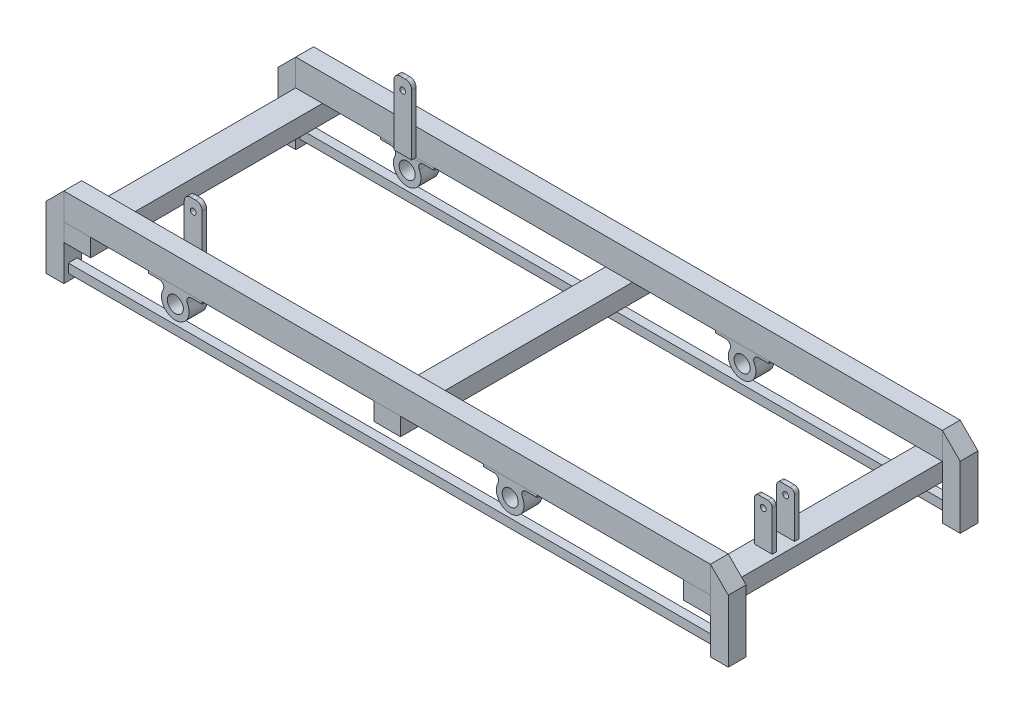
SolidWorks part; units mm, degrees
ref_plane "Front Plane" through (0, 0, 0) normal (0, 0, 1) x (1, 0, 0)
ref_plane "Top Plane" through (0, 0, 0) normal (0, 1, 0) x (1, 0, 0)
ref_plane "Right Plane" through (0, 0, 0) normal (1, 0, 0) x (0, 0, -1)
sketch "Sketch1" plane through (0, 0, 0) normal (0, 1, 0) x (1, 0, 0)
  line L0 (0, 236.3265) -> (0, -239.5918) construction
  line L1 (-360.8163, 0) -> (346.9388, 0) construction
  line L2 (-765, 280) -> (-725, 280)
  line L3 (-765, 280) -> (-765, 240)
  line L4 (-765, 240) -> (-725, 240)
  line L5 (-725, 280) -> (-725, 240)
  line L6 (-725, -280) -> (-725, -240)
  line L7 (-765, -240) -> (-725, -240)
  line L8 (-765, -280) -> (-765, -240)
  line L9 (-765, -280) -> (-725, -280)
  line L10 (765, -280) -> (725, -280)
  line L11 (765, -280) -> (765, -240)
  line L12 (765, -240) -> (725, -240)
  line L13 (725, -280) -> (725, -240)
  line L14 (725, 280) -> (725, 240)
  line L15 (765, 240) -> (725, 240)
  line L16 (765, 280) -> (765, 240)
  line L17 (765, 280) -> (725, 280)
  point P9 (-765, 260)
  dimension "D1" = 40
  dimension "D2" = 560
  dimension "D3" = 1530
extrude "Boss-Extrude1" add sketch "Sketch1" against normal blind 180
chamfer "Chamfer1" distance 40 angle 45 1 edges at (-765, 0, -260)
chamfer "Chamfer2" distance 40 angle 45 1 edges at (-765, 0, 260)
chamfer "Chamfer3" distance 40 angle 45 1 edges at (765, 0, -260)
chamfer "Chamfer4" distance 40 angle 45 1 edges at (765, 0, 260)
sketch "Sketch2" plane through (0, 0, 280) normal (0, 0, 1) x (1, 0, 0)
  line L0 (725, -180) -> (725, 0) construction
  line L1 (-725, 0) -> (725, 0)
  line L2 (-725, 0) -> (-725, -60)
  line L3 (-725, -60) -> (725, -60)
  line L4 (725, 0) -> (725, -60)
  dimension "D1" = 60
extrude "Boss-Extrude2" add sketch "Sketch2" against normal blind 40 separate body
mirror "Mirror2" about plane through (0, 0, 0) normal (0, 0, 1) of bodies 105
sketch "Sketch3" plane through (0, 0, 280) normal (0, 0, 1) x (1, 0, 0)
  line L0 (0, 430.6233) -> (0, -418.6092) construction
  line L1 (725, -60) -> (665, -60)
  line L2 (725, -60) -> (725, -100)
  line L3 (725, -100) -> (665, -100)
  line L4 (665, -60) -> (665, -100)
  line L5 (-665, -60) -> (-665, -100)
  line L6 (-725, -100) -> (-665, -100)
  line L7 (-725, -60) -> (-725, -100)
  line L8 (-725, -60) -> (-665, -60)
  line L9 (-725, -60) -> (725, -60) construction
  line L10 (-30, -60) -> (30, -60)
  line L11 (-30, -60) -> (-30, -100)
  line L12 (-30, -100) -> (30, -100)
  line L13 (30, -60) -> (30, -100)
  dimension "D1" = 60
  dimension "D2" = 40
  dimension "D3" = 40
  dimension "D4" = 60
extrude "Boss-Extrude3" add sketch "Sketch3" against normal up to surface (560 mm away) separate body up to face at (0, -30, -280)
sketch "Sketch4" plane through (-725, 0, 0) normal (1, 0, 0) x (0, 0, -1)
  line L0 (-260, 0) -> (-260, -180) construction
  line L1 (-270, -145) -> (-250, -145)
  line L2 (-270, -145) -> (-270, -165)
  line L3 (-270, -165) -> (-250, -165)
  line L4 (-250, -145) -> (-250, -165)
  line L5 (-270, -145) -> (-250, -165) construction
  line L6 (-270, -165) -> (-250, -145) construction
  line L7 (-240, 0) -> (-280, 0) construction
  line L8 (-280, -180) -> (-240, -180) construction
  line L9 (0, 126.0485) -> (0, -222.351) construction
  line L10 (270, -165) -> (250, -145) construction
  line L11 (270, -145) -> (250, -165) construction
  line L12 (250, -145) -> (250, -165)
  line L13 (270, -165) -> (250, -165)
  line L14 (270, -145) -> (270, -165)
  line L15 (270, -145) -> (250, -145)
  point P0 (-260, -155)
  point P18 (260, -155)
  dimension "D1" = 20
  dimension "D2" = 25
extrude "Boss-Extrude4" add sketch "Sketch4" along normal up to surface (1450 mm away) up to face at (725, -90, 260)
sketch "Sketch5" plane through (0, 0, -240) normal (0, 0, 1) x (1, 0, 0)
  line L0 (-725, -60) -> (725, -60) construction
  line L1 (-495, -60) -> (-455, -60)
  line L2 (-495, -60) -> (-495, 76)
  line L3 (-481, 90) -> (-469, 90)
  line L4 (-455, -60) -> (-455, 76)
  line L5 (-765, -180) -> (-765, -40) construction
  line L6 (-475, 90) -> (-475, 65) construction
  arc A0 (-469, 90) -> (-455, 76) centre (-469, 76) cw
  arc A1 (-495, 76) -> (-481, 90) centre (-481, 76) cw
  circle A2 centre (-475, 65) radius 6.5
  point P6 (-475, -60)
  point P11 (-455, 90)
  point P14 (-495, 90)
  point P17 (-475, 90)
  dimension "D4" = 14
  dimension "D6" = 13
  dimension "D1" = 150
  dimension "D2" = 310
  dimension "D3" = 40
  dimension "D5" = 25
extrude "Boss-Extrude5" add sketch "Sketch5" along normal blind 10 separate body
mirror "Mirror4" about plane through (0, 0, 0) normal (0, 0, 1) of bodies 112
sketch "Sketch6" plane through (0, -60, 0) normal (0, -1, 0) x (1, 0, 0)
  line L0 (-475, 240) -> (-475, 280) construction
  line L2 (-725, 280) -> (725, 280) construction
  line L3 (-495, 240) -> (-455, 240) construction
  line L4 (-725, 240) -> (725, 240) construction
  line L5 (-535, 280) -> (-415, 280)
  line L6 (-535, 280) -> (-535, 240)
  line L7 (-535, 240) -> (-415, 240)
  line L8 (-415, 280) -> (-415, 240)
  line L9 (-535, 280) -> (-415, 240) construction
  line L10 (-535, 240) -> (-415, 280) construction
  line L11 (-936.0603, 0) -> (959.9597, 0) construction
  line L12 (-535, -240) -> (-415, -280) construction
  line L13 (-535, -280) -> (-415, -240) construction
  line L14 (-475, -240) -> (-475, -280) construction
  line L15 (-415, -280) -> (-415, -240)
  line L16 (-535, -240) -> (-415, -240)
  line L17 (-535, -280) -> (-535, -240)
  line L18 (-535, -280) -> (-415, -280)
  point P8 (-475, 260)
  point P22 (-475, -260)
  dimension "D1" = 120
extrude "Boss-Extrude6" add sketch "Sketch6" along normal blind 5 separate body
sketch "Sketch7" plane through (0, 0, 280) normal (0, 0, 1) x (1, 0, 0)
  line L0 (-475, -65) -> (-475, -95) construction
  line L1 (-415, -65) -> (-535, -65) construction
  circle A0 centre (-475, -95) radius 31
  circle A1 centre (-475, -95) radius 18
  dimension "D1" = 30
  dimension "D2" = 62
  dimension "D3" = 36
extrude "Boss-Extrude7" add sketch "Sketch7" against normal up to surface (40 mm away) up to face at (-475, -62.5, 240)
fillet "Fillet1" radius 10 2 edges at (-467.1898, -65, 260) (-482.8102, -65, 260)
mirror "Mirror6" about plane through (0, 0, 0) normal (0, 0, 1) of bodies 116
sketch "Sketch9" plane through (0, 0, 280) normal (0, 0, 1) x (1, 0, 0)
  line L5 (-725, -60) -> (725, -60) construction
  line L6 (245, -95) -> (245, 15.9014) construction
  line L7 (765, -180) -> (765, -40) construction
  line B0 (336, -65) -> (336, -60)
  line B1 (336, -65) -> (311.7911, -65)
  line B2 (216, -65) -> (216, -60)
  line B3 (240.2089, -65) -> (216, -65)
  line B4 (336, -60) -> (216, -60)
  circle B5 centre (276, -95) radius 18
  arc B6 (311.7911, -65) -> (303.0615, -79.878) centre (311.7911, -75) ccw
  arc B7 (248.9385, -79.878) -> (303.0615, -79.878) centre (276, -95) ccw
  arc B8 (248.9385, -79.878) -> (240.2089, -65) centre (240.2089, -75) ccw
  dimension "D1" = 520
sketch_block_instance "Block1-2"
sketch_block "Block1" parameters "D1"=52, "D2"=26
extrude "Boss-Extrude8" add sketch "Sketch9" against normal up to surface (40 mm away) separate body up to face at (0, -30, 240)
mirror "Mirror7" about plane through (0, 0, 0) normal (0, 0, 1) of bodies 118
ref_plane "Plane1" through (695, 0, 0) normal (1, 0, 0) x (0, 0, -1)
sketch "Sketch10" plane through (695, 0, 0) normal (1, 0, 0) x (0, 0, -1)
  line L6 (-71.4052, 40) -> (-81.4052, 40)
  line L7 (-71.4052, -60) -> (-71.4052, 40)
  line L8 (-81.4052, 40) -> (-81.4052, -60)
  line L9 (-131.4052, 40) -> (-122.4052, 40)
  line L10 (-122.4052, 40) -> (-122.4052, -60)
  line L11 (-131.4052, -60) -> (-131.4052, 40)
  line L12 (-131.4052, -60) -> (-122.4052, -60)
  line L13 (-81.4052, -60) -> (-71.4052, -60)
  dimension "D1" = 41
  dimension "D2" = 10
  dimension "D3" = 60
extrude "Boss-Extrude9" add sketch "Sketch10" along normal mid plane 40
fillet "Fillet2" radius 10 4 edges at (675, 40, 76.4052) (715, 40, 76.4052) (675, 40, 126.9052) (715, 40, 126.9052)
sketch "Sketch11" plane through (0, 0, 131.4052) normal (0, 0, 1) x (1, 0, 0)
  line L0 (695, 40) -> (695, -17.024) construction
  line L1 (705, 40) -> (685, 40) construction
  circle A0 centre (695, 20) radius 6.5
  dimension "D1" = 13
  dimension "D2" = 20
extrude "Cut-Extrude1" cut sketch "Sketch11" against normal blind 62
